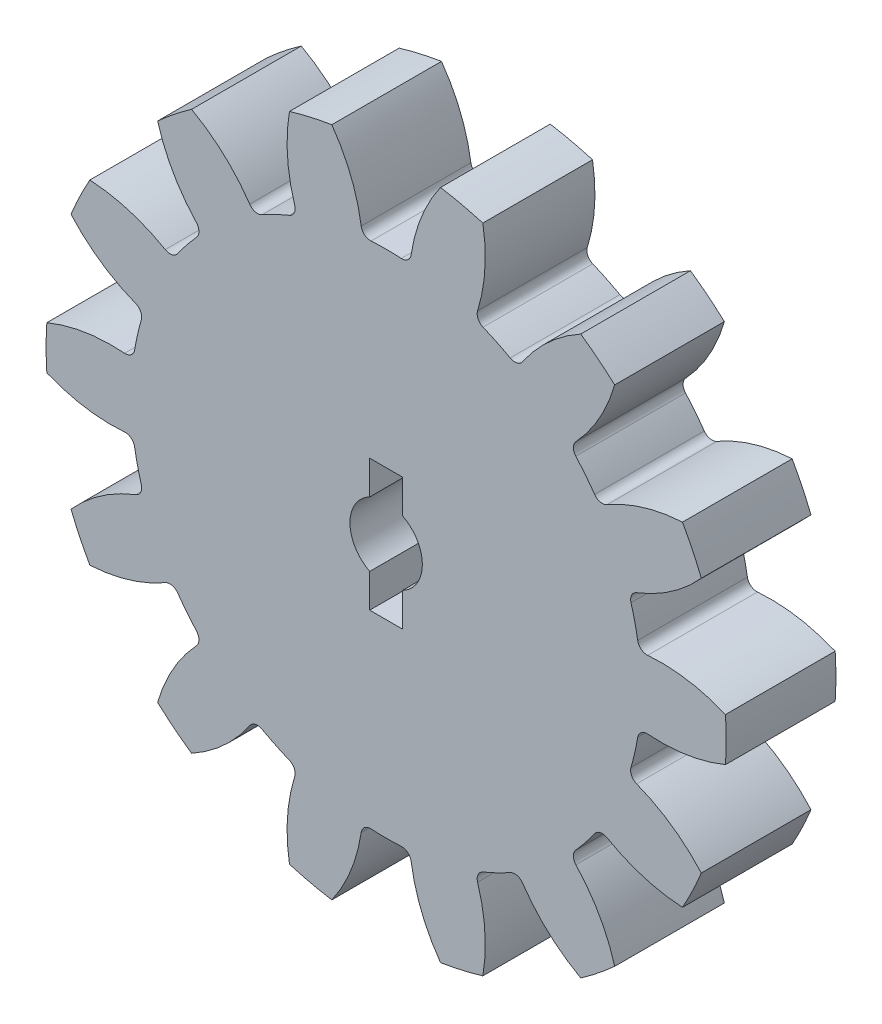
SolidWorks part; units mm, degrees
ref_plane "Front" through (0, 0, 0) normal (0, 0, 1) x (1, 0, 0)
ref_plane "Top" through (0, 0, 0) normal (0, 1, 0) x (1, 0, 0)
ref_plane "Right" through (0, 0, 0) normal (1, 0, 0) x (0, 0, -1)
sketch "Sketch1" plane through (0, 0, 0) normal (0, 0, 1) x (1, 0, 0)
  circle A0 centre (0, 0) radius 11.625
  circle A1 centre (0, 0) radius 15.5
  circle A2 centre (0, 0) radius 13.5625
  dimension "D1" = 31
  dimension "D2" = 23.25
  dimension "D3" = 27.125
extrude "Boss-Extrude1" add sketch "Sketch1" along normal mid plane 5 contours A1
sketch "Sketch3" plane through (0, 0, 0) normal (0, 0, 1) x (1, 0, 0)
  line L0 (0, 0) -> (0, 15.5) construction
  line L1 (0, 0) -> (-1.0899, 11.5738) construction
  line L2 (-1.5185, 13.4772) -> (1.5185, 13.4772) construction
  line L3 (-2.1978, 15.3434) -> (0, 9.3051) construction
  line L4 (1.5185, 13.4772) -> (4.4794, 12.8014) construction
  line L5 (3.4491, 15.1114) -> (0, 0) construction
  arc A0 (-1.0899, 11.5738) -> (1.0899, 11.5738) centre (0, 0) cw
  arc A4 (2.4768, 15.3008) -> (-2.4768, 15.3008) centre (0, 0) ccw
  circle A5 centre (0, 0) radius 15.5 construction
  arc A7 (-2.4768, 15.3008) -> (-1.0899, 11.5738) centre (-8.7231, 10.855) cw
  arc A10 (2.4768, 15.3008) -> (1.0899, 11.5738) centre (8.7231, 10.855) ccw
  circle A11 centre (0, 0) radius 11.625 construction
  circle A12 centre (0, 0) radius 13.5625 construction
  dimension "D1" = 20
  dimension "D2" = 12.857
extrude "Cut-Extrude1" cut sketch "Sketch3" against normal through all both and the other way through all contours A10 A4 A7 A0 region at (0, 13.804, 0)
fillet "Fillet2" radius 0.43 2 edges at (-1.0899, 11.5738, 0) (1.0899, 11.5738, 0)
pattern_circular "CirPattern1" count 14 over 360 about axis through (0, 0, 2.5) along (0, 0, -1) of "Cut-Extrude1", "Fillet2"
sketch "Sketch4" plane through (0, 0, 0) normal (0, 0, 1) x (1, 0, 0)
  line L0 (-0.75, 3) -> (0.75, 3)
  line L1 (-0.75, -3) -> (0.75, -3) construction
  line L3 (-0.75, 3) -> (0.75, 3) construction
  line L7 (0.75, 3) -> (0.75, 1.4697)
  line L8 (-0.75, 3) -> (-0.75, 1.4697)
  line L9 (-0.75, -1.4697) -> (-0.75, -3)
  line L10 (-0.75, -3) -> (0.75, -3)
  line L11 (0.75, -3) -> (0.75, -1.4697)
  arc A1 (-0.75, 1.4697) -> (-0.75, -1.4697) centre (0, 0) ccw
  arc A2 (0.75, 1.4697) -> (0.75, -1.4697) centre (0, 0) cw
  dimension "D1" = 1.65
  dimension "D4" = 1.65
  dimension "D2" = 6
  dimension "D3" = 1.5
  dimension "D5" = 1.5
  dimension "D6" = 1.5303
extrude "Through_Center_Hole" cut sketch "Sketch4" against normal through all both and the other way through all
sketch "Sketch5" plane through (0, 0, 2.5) normal (0, 0, 1) x (1, 0, 0)
  circle A0 centre (0, 0) radius 1.6476
  dimension "D1" = 3.2952
equation "\"od\" = 31'outside diameter"
equation "\"n\"= 14'number of teeth"
equation "\"m\"= \"od\" / ( \"n\" + 2 )'module"
equation "\"p\"= \"m\" * pi'pitch"
equation "\"d\"= \"m\" * \"n\"'primitive diameter"
equation "\"da\"= \"d\" + 2 * \"m\"'head diamater"
equation "\"df\"= \"d\" - 2 * \"m\"'foot diameter"
equation "\"D1@Sketch1\"=\"od\""
equation "\"D2@Sketch1\"=\"df\""
equation "\"D3@Sketch1\"=\"d\""
equation "\"D2@Sketch3\"=180/\"n\""
equation "\"D1@CirPattern1\"=\"n\""
